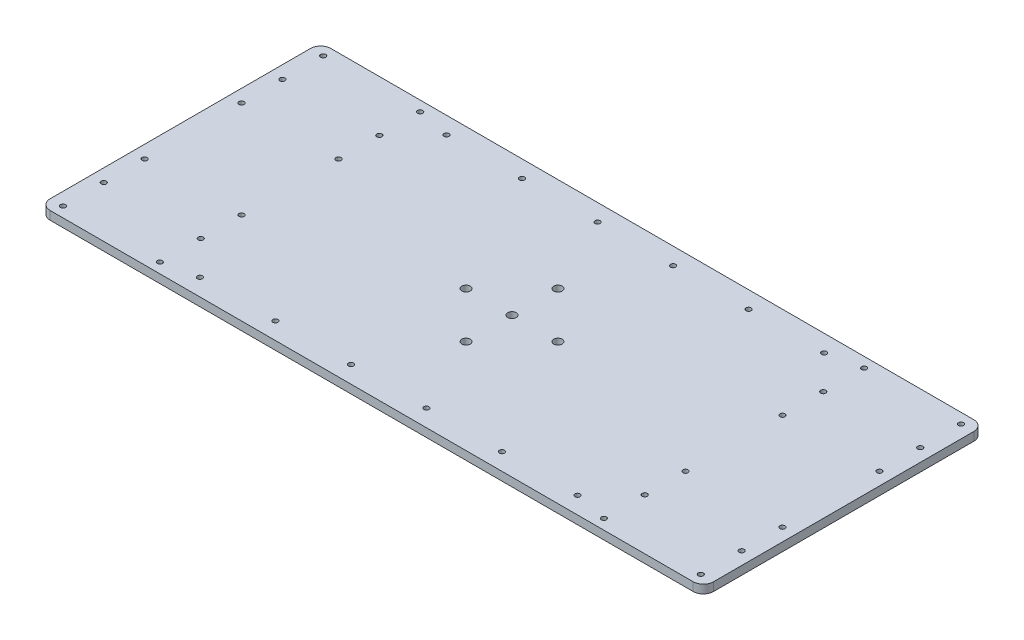
SolidWorks part; units mm, degrees
ref_plane "Front Plane" through (0, 0, 0) normal (0, 0, 1) x (1, 0, 0)
ref_plane "Top Plane" through (0, 0, 0) normal (0, 1, 0) x (1, 0, 0)
ref_plane "Right Plane" through (0, 0, 0) normal (1, 0, 0) x (0, 0, -1)
sketch "Sketch1" plane through (0, 0, 0) normal (0, 1, 0) x (1, 0, 0)
  line L0 (-187.5, 82.5) -> (-187.5, -82.5) construction
  line L1 (-189, -82.5) -> (189, -82.5)
  line L2 (-195, -76.5) -> (-195, 76.5)
  line L3 (-189, 82.5) -> (189, 82.5)
  line L4 (195, -76.5) -> (195, 76.5)
  line L5 (-195, -82.5) -> (195, 82.5) construction
  line L6 (-195, 82.5) -> (195, -82.5) construction
  line L7 (0, 0) -> (-30, -30) construction
  line L8 (0, 82.5) -> (0, -82.5) construction
  line L9 (-195, 0) -> (195, 0) construction
  line L10 (-9.5, -10) -> (9.5, -10) construction
  line L11 (-10, -9.5) -> (-10, 9.5) construction
  line L12 (-9.5, 10) -> (9.5, 10) construction
  line L13 (10, -9.5) -> (10, 9.5) construction
  line L14 (-10, -10) -> (10, 10) construction
  line L15 (-10, 10) -> (10, -10) construction
  line L16 (-123, 82.5) -> (-123, -82.5) construction
  line L17 (-123, -72.5) -> (0, -72.5) construction
  circle A0 centre (-187.5, 76.5) radius 1.5
  circle A1 centre (-187.5, 52.5) radius 1.5
  circle A2 centre (-187.5, 28.5) radius 1.5
  circle A3 centre (-130.5, 76.5) radius 1.5
  circle A4 centre (-130.5, 52.5) radius 1.5
  circle A5 centre (-130.5, 28.5) radius 1.5
  circle A6 centre (130.5, 28.5) radius 1.5
  circle A7 centre (130.5, 52.5) radius 1.5
  circle A8 centre (130.5, 76.5) radius 1.5
  circle A9 centre (187.5, 28.5) radius 1.5
  circle A10 centre (187.5, 52.5) radius 1.5
  circle A11 centre (187.5, 76.5) radius 1.5
  circle A12 centre (187.5, -76.5) radius 1.5
  circle A13 centre (187.5, -52.5) radius 1.5
  circle A14 centre (187.5, -28.5) radius 1.5
  circle A15 centre (130.5, -76.5) radius 1.5
  circle A16 centre (130.5, -52.5) radius 1.5
  circle A17 centre (130.5, -28.5) radius 1.5
  circle A18 centre (-130.5, -28.5) radius 1.5
  circle A19 centre (-130.5, -52.5) radius 1.5
  circle A20 centre (-130.5, -76.5) radius 1.5
  circle A21 centre (-187.5, -28.5) radius 1.5
  circle A22 centre (-187.5, -52.5) radius 1.5
  circle A23 centre (-187.5, -76.5) radius 1.5
  arc A24 (9.5, 10) -> (10, 9.5) centre (9.5, 9.5) cw construction
  arc A25 (10, -9.5) -> (9.5, -10) centre (9.5, -9.5) cw construction
  arc A26 (-9.5, -10) -> (-10, -9.5) centre (-9.5, -9.5) cw construction
  arc A27 (-10, 9.5) -> (-9.5, 10) centre (-9.5, 9.5) cw construction
  circle A28 centre (0, 27) radius 2.5
  circle A29 centre (27, 0) radius 2.5
  circle A30 centre (0, -27) radius 2.5
  circle A31 centre (-27, 0) radius 2.5
  circle A32 centre (0, 0) radius 2.5
  circle A33 centre (-30, -30) radius 2.5 construction
  circle A34 centre (-30, 30) radius 2.5 construction
  circle A35 centre (30, 30) radius 2.5 construction
  circle A36 centre (30, -30) radius 2.5 construction
  arc A37 (189, 82.5) -> (195, 76.5) centre (189, 76.5) cw
  arc A38 (195, -76.5) -> (189, -82.5) centre (189, -76.5) cw
  arc A39 (-189, -82.5) -> (-195, -76.5) centre (-189, -76.5) cw
  arc A40 (-195, 76.5) -> (-189, 82.5) centre (-189, 76.5) cw
  circle A41 centre (-111, -72.5) radius 1.5
  circle A45 centre (-66.6, -72.5) radius 1.5
  circle A46 centre (-22.2, -72.5) radius 1.5
  circle A47 centre (22.2, -72.5) radius 1.5
  circle A48 centre (66.6, -72.5) radius 1.5
  circle A49 centre (111, -72.5) radius 1.5
  circle A50 centre (111, 72.5) radius 1.5
  circle A51 centre (66.6, 72.5) radius 1.5
  circle A52 centre (22.2, 72.5) radius 1.5
  circle A53 centre (-22.2, 72.5) radius 1.5
  circle A54 centre (-66.6, 72.5) radius 1.5
  circle A55 centre (-111, 72.5) radius 1.5
  point P0 (0, 0)
  point P59 (0, 0)
  point P88 (0, 0)
  point P98 (0, 0)
  dimension "D5" = 3
  dimension "D9" = 0.5
  dimension "D10" = 17
  dimension "D11" = 5
  dimension "D14" = 57
  dimension "D15" = 45
  dimension "D17" = 60
  dimension "D18" = 5
  dimension "D19" = 6
  dimension "D22" = 3
  dimension "D23" = 12
  dimension "D25" = 44.4
  dimension "D1" = 390
  dimension "D2" = 165
  dimension "D3" = 7.5
  dimension "D4" = 3
  dimension "D6" = 6
  dimension "D8" = 20
  dimension "D13" = 24
  dimension "D20" = 72
  dimension "D21" = 10
  dimension "D24" = 6
  dimension "D7" = 2
  dimension "D12" = 4
  dimension "D16" = 4
extrude "Boss-Extrude1" add sketch "Sketch1" along normal blind 5
